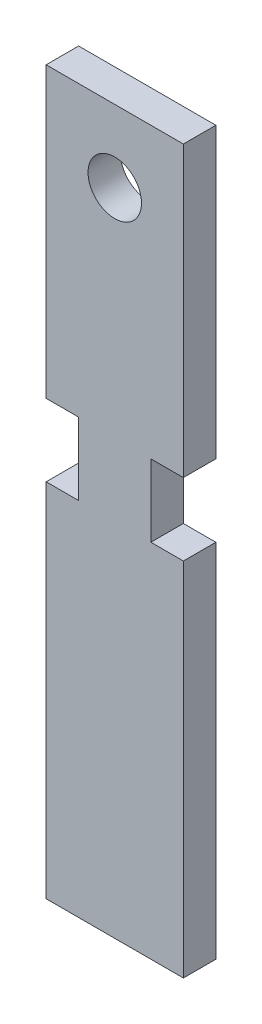
SolidWorks part; units mm, degrees
ref_plane "Front Plane" through (0, 0, 0) normal (0, 0, 1) x (1, 0, 0)
ref_plane "Top Plane" through (0, 0, 0) normal (0, 1, 0) x (1, 0, 0)
ref_plane "Right Plane" through (0, 0, 0) normal (1, 0, 0) x (0, 0, -1)
sketch "Sketch1" plane through (0, 0, 0) normal (0, 0, 1) x (1, 0, 0)
  line L0 (-25.4, 63.5) -> (-25.4, -63.5)
  line L5 (-25.4, 63.5) -> (25.4, 63.5)
  line L6 (-25.4, -63.5) -> (25.4, -63.5)
  line L7 (25.4, 63.5) -> (25.4, -63.5)
  line L8 (-25.4, 0) -> (25.4, 0) construction
  point P0 (0, 0)
  point P13 (-25.4, 0)
  point P14 (0, 0)
  dimension "D3" = 50.8
extrude "Boss-Extrude1" add sketch "Sketch1" along normal blind 5.715
sketch "Sketch2" plane through (0, 0, 5.715) normal (0, 0, 1) x (1, 0, 0)
  line L4 (-12.065, 0) -> (-6.35, 0)
  line L5 (-12.065, 0) -> (-12.065, 12.7)
  line L6 (-12.065, 12.7) -> (-6.35, 12.7)
  line L7 (-6.35, 0) -> (-6.35, 12.7)
  line L8 (-12.065, 0) -> (-6.35, 12.7) construction
  line L9 (-12.065, 12.7) -> (-6.35, 0) construction
  line L11 (0, -3.1432) -> (0, 3.1432) construction
  line L12 (12.065, 0) -> (6.35, 0)
  line L13 (12.065, 0) -> (12.065, 12.7)
  line L14 (12.065, 12.7) -> (6.35, 12.7)
  line L15 (6.35, 0) -> (6.35, 12.7)
  line L17 (-25.4, -63.5) -> (25.4, -63.5) construction
  circle A0 centre (0, 50.8) radius 4.699
  point P3 (0, -63.5)
  point P5 (-9.2075, 6.35)
  dimension "D2" = 9.398
  dimension "D1" = 114.3
  dimension "D3" = 63.5
  dimension "D4" = 12.7
  dimension "D5" = 5.715
  dimension "D6" = 6.35
  dimension "D7" = 6.35
extrude "Cut-Extrude1" cut sketch "Sketch2" against normal through all
sketch "Sketch3" plane through (0, 0, 5.715) normal (0, 0, 1) x (1, 0, 0)
  line L0 (-12.065, 63.5) -> (12.065, 63.5)
  line L1 (25.4, 63.5) -> (-25.4, 63.5) construction
  line L2 (-12.065, 63.5) -> (-12.065, -63.5)
  line L3 (-25.4, -63.5) -> (25.4, -63.5) construction
  line L4 (12.065, 63.5) -> (12.065, -63.5)
  line L5 (-12.065, -63.5) -> (12.065, -63.5)
  line L6 (-12.065, 12.7) -> (-12.065, 0) construction
  line L7 (12.065, 0) -> (12.065, 12.7) construction
  line M9 (-12.065, 0) -> (-12.065, 12.7)
  line M11 (12.065, 12.7) -> (12.065, 0)
  line M14 (25.4, 63.5) -> (-25.4, 63.5)
  line M15 (-25.4, 63.5) -> (-25.4, -63.5)
  line M16 (-25.4, -63.5) -> (25.4, -63.5)
  line M17 (25.4, -63.5) -> (25.4, 63.5)
extrude "Cut-Extrude2" cut sketch "Sketch3" against normal through all contours L2 M14 M15 M16 M9 | L4 M14 M11 M16 M17 region at (-18.7325, 0, 5.715) region at (18.7325, 0, 5.715)
